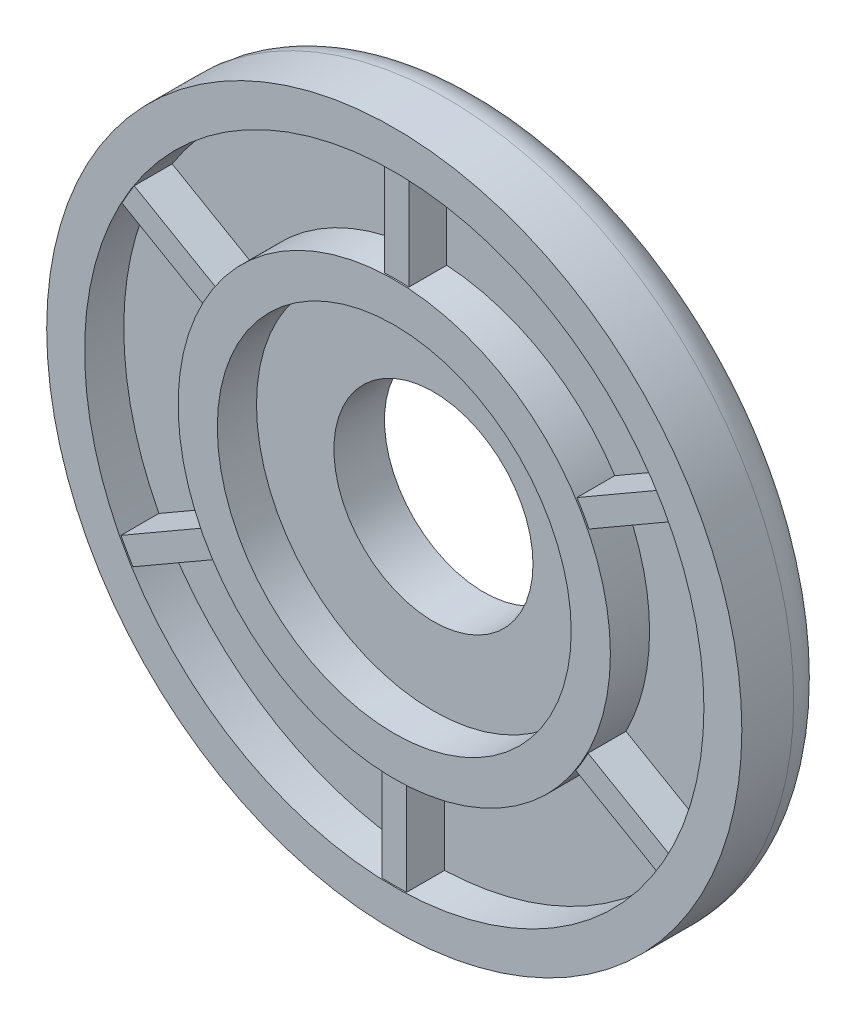
SolidWorks part; units mm, degrees
ref_plane "Спереди" through (0, 0, 0) normal (0, 0, 1) x (1, 0, 0)
ref_plane "Сверху" through (0, 0, 0) normal (0, 1, 0) x (1, 0, 0)
ref_plane "Справа" through (0, 0, 0) normal (1, 0, 0) x (0, 0, -1)
other "Configuration Table"
sketch "Эскиз1" plane through (0, 0, 0) normal (0, 0, 1) x (1, 0, 0)
  circle A0 centre (0, 0) radius 27.5
  circle A1 centre (0, 0) radius 7.875
  dimension "D1" = 55
  dimension "D2" = 15.75
extrude "Бобышка-Вытянуть1" add sketch "Эскиз1" along normal blind 4
sketch "Эскиз2" plane through (0, 0, 4) normal (0, 0, 1) x (1, 0, 0)
  circle A0 centre (0, 0) radius 27.5
  circle A1 centre (0, 0) radius 24.5
  circle A2 centre (0, 0) radius 17.1
  circle A3 centre (0, 0) radius 14
  circle M3 centre (0, 0) radius 27.5
  dimension "D1" = 55
  dimension "D2" = 49
  dimension "D3" = 34.2
  dimension "D4" = 28
extrude "Бобышка-Вытянуть2" add sketch "Эскиз2" along normal blind 3.1 and the other way blind 3.1 contours A1 M3 | A2 A3 region at (-26.7222, 0, 4) region at (-16.6163, 0, 4)
sketch "Эскиз4" plane through (0, 0, 4) normal (0, 0, 1) x (1, 0, 0)
  line L0 (0, 35.1842) -> (0, -39.1076) construction
  line L1 (-0.8785, 24.9307) -> (-0.8785, 16.6554)
  line L2 (-0.8785, 16.6554) -> (1.0515, 16.6554)
  line L3 (1.0515, 16.6554) -> (1.0515, 24.9307)
  line L4 (1.0515, 24.9307) -> (-0.8785, 24.9307)
  line L5 (22.1163, 11.5548) -> (21.1513, 13.2262)
  line L6 (21.1513, 13.2262) -> (13.9848, 9.0886)
  line L7 (13.9848, 9.0886) -> (14.9498, 7.4171)
  line L8 (14.9498, 7.4171) -> (22.1163, 11.5548)
  line L9 (21.0649, -13.3759) -> (22.0299, -11.7045)
  line L10 (22.0299, -11.7045) -> (14.8633, -7.5669)
  line L11 (14.8633, -7.5669) -> (13.8983, -9.2383)
  line L12 (13.8983, -9.2383) -> (21.0649, -13.3759)
  line L13 (-1.0515, -24.9307) -> (0.8785, -24.9307)
  line L14 (0.8785, -24.9307) -> (0.8785, -16.6554)
  line L15 (0.8785, -16.6554) -> (-1.0515, -16.6554)
  line L16 (-1.0515, -16.6554) -> (-1.0515, -24.9307)
  line L17 (-22.1163, -11.5548) -> (-21.1513, -13.2262)
  line L18 (-21.1513, -13.2262) -> (-13.9848, -9.0886)
  line L19 (-13.9848, -9.0886) -> (-14.9498, -7.4171)
  line L20 (-14.9498, -7.4171) -> (-22.1163, -11.5548)
  line L21 (-21.0649, 13.3759) -> (-22.0299, 11.7045)
  line L22 (-22.0299, 11.7045) -> (-14.8633, 7.5669)
  line L23 (-14.8633, 7.5669) -> (-13.8983, 9.2383)
  line L24 (-13.8983, 9.2383) -> (-21.0649, 13.3759)
  point P30 (0, 0)
  dimension "D1" = 1.93
extrude "Бобышка-Вытянуть6" add sketch "Эскиз4" along normal blind 3
fillet "Скругление1" radius 3 1 edges at (27.5, 0, 0)
